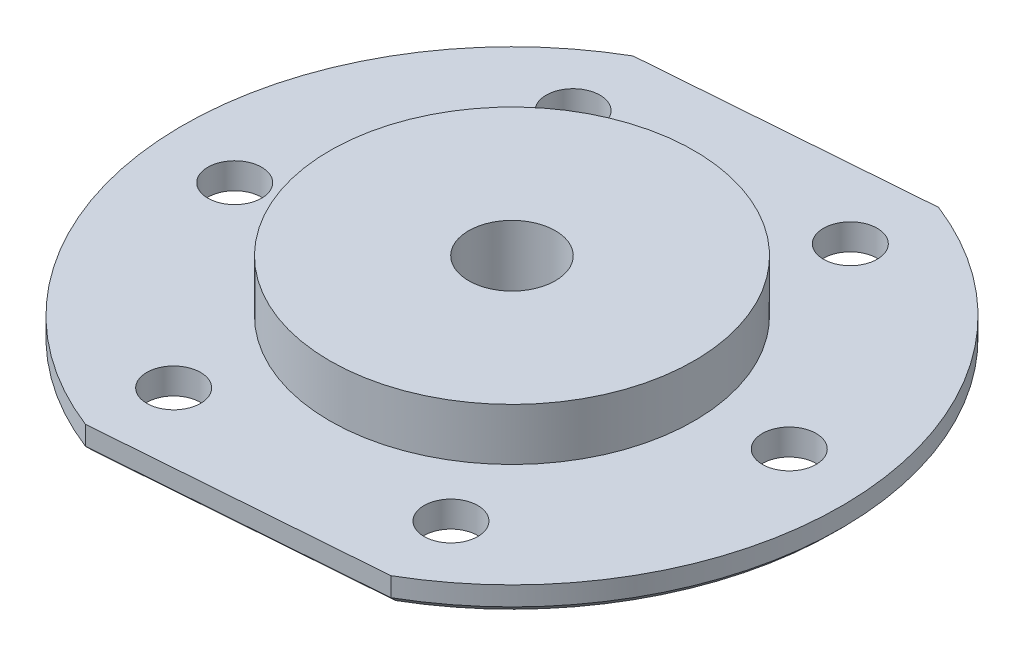
SolidWorks part; units mm, degrees
ref_plane "Front Plane" through (0, 0, 0) normal (0, 0, 1) x (1, 0, 0)
ref_plane "Top Plane" through (0, 0, 0) normal (0, 1, 0) x (1, 0, 0)
ref_plane "Right Plane" through (0, 0, 0) normal (1, 0, 0) x (0, 0, -1)
sketch "Sketch1" plane through (0, 0, 0) normal (0, 1, 0) x (1, 0, 0)
  circle A0 centre (0, 0) radius 19
  circle A1 centre (0, 0) radius 10
  dimension "D1" = 38
  dimension "D2" = 20
extrude "Boss-Extrude1" add sketch "Sketch1" along normal blind 1.5
sketch "Sketch2" plane through (0, 1.5, 0) normal (0, 1, 0) x (1, 0, 0)
  line L0 (-9.4832, 16.4642) -> (6.8785, 17.7112)
  line L5 (-8.485, 26.5236) -> (0, 0) construction
  line L6 (0, 0) -> (8.485, 26.5236) construction
  line L7 (6.8785, 17.7112) -> (6.6452, 20.7724)
  line L8 (6.6452, 20.7724) -> (-9.4832, 19.5431)
  line L9 (-9.4832, 19.5431) -> (-9.4832, 16.4642)
  line L10 (-7.0461, -0.537) -> (7.6149, 0.5804) construction
  line L11 (9.4832, -16.4642) -> (9.7166, -19.5254)
  line L12 (9.7166, -19.5254) -> (-6.4119, -20.7546)
  line L13 (-6.4119, -20.7546) -> (-6.8785, -17.7112)
  line L14 (-6.8785, -17.7112) -> (9.4832, -16.4642)
  circle A0 centre (-8.485, 12.0053) radius 1.55
  circle A3 centre (6.1544, 13.3509) radius 1.55
  circle A4 centre (14.6394, 1.3456) radius 1.55
  circle A5 centre (8.485, -12.0053) radius 1.55
  circle A6 centre (-6.1544, -13.3509) radius 1.55
  circle A7 centre (-14.6394, -1.3456) radius 1.55
  circle A9 centre (0, 0) radius 19 construction
  point P3 (0, 0)
  point P17 (0, 0)
  dimension "D1" = 3.1
  dimension "D2" = 6
extrude "Cut-Extrude1" cut sketch "Sketch2" against normal through all
sketch "Sketch3" plane through (0, 1.5, 0) normal (0, 1, 0) x (1, 0, 0)
  circle A0 centre (0, 0) radius 10.5
  circle A1 centre (0, 0) radius 10 construction
  circle A2 centre (0, 0) radius 10
  dimension "D1" = 21
extrude "Boss-Extrude2" add sketch "Sketch3" along normal blind 3 contours A0
chamfer "Chamfer2" distance 0.4 angle 45 4 edges at (1.3024, 0, 17.0877) (-18.9451, 0, 1.4439) (18.9451, 0, -1.4439) (-1.3024, 0, -17.0877)
sketch "Sketch4" plane through (0, 1.5, 0) normal (0, -1, 0) x (1, 0, 0)
  circle A0 centre (0, 0) radius 5
  circle A1 centre (0, 0) radius 2.5
  dimension "D1" = 10
  dimension "D2" = 5
extrude "Boss-Extrude3" add sketch "Sketch4" along normal blind 3 contours A0
extrude "Cut-Extrude2" cut sketch "Sketch4<3>" against normal through all both and the other way through all contours A1
sketch "Sketch4<3>" plane through (0, 1.5, 0) normal (0, -1, 0) x (1, 0, 0) same geometry as "Sketch4"
